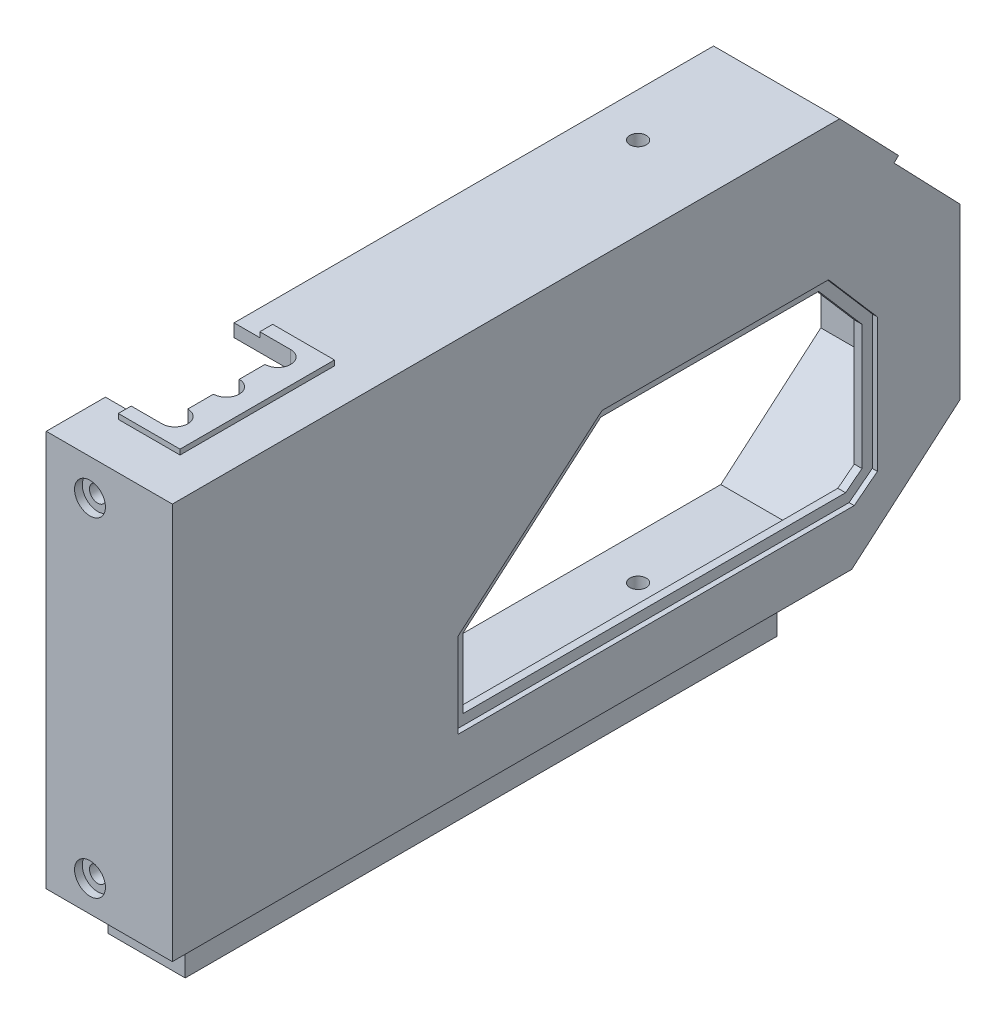
SolidWorks part; units mm, degrees
ref_plane "Front Plane" through (0, 0, 0) normal (0, 0, 1) x (1, 0, 0)
ref_plane "Top Plane" through (0, 0, 0) normal (0, 1, 0) x (1, 0, 0)
ref_plane "Right Plane" through (0, 0, 0) normal (1, 0, 0) x (0, 0, -1)
sketch "Sketch1" plane through (0, 0, 0) normal (1, 0, 0) x (0, 0, -1)
  line L0 (0, 0) -> (0, 77)
  line L1 (0, 77) -> (128, 77)
  line L2 (128, 77) -> (153, 51)
  line L3 (153, 51) -> (153, 18)
  line L4 (153, 18) -> (132, 0)
  line L5 (132, 0) -> (0, 0)
  dimension "D1" = 132
  dimension "D2" = 77
  dimension "D3" = 128
  dimension "D4" = 26
  dimension "D5" = 153
  dimension "D6" = 18
extrude "Base" add sketch "Sketch1" along normal blind 2.5
sketch "Sketch11" plane through (0, 0, 0) normal (-1, 0, 0) x (0, 0, 1)
  line L12 (-131.0752, 2.5) -> (-2.5, 2.5)
  line L13 (-2.5, 2.5) -> (-2.5, 74.5)
  line L14 (-2.5, 74.5) -> (-126.9356, 74.5)
  line L15 (-126.9356, 74.5) -> (-150.5, 49.9931)
  line L16 (-150.5, 49.9931) -> (-150.5, 19.1498)
  line L17 (-150.5, 19.1498) -> (-131.0752, 2.5)
  line L18 (-131.0752, 2.5) -> (-2.5, 2.5)
  line L19 (-2.5, 2.5) -> (-2.5, 74.5)
  line L20 (-2.5, 74.5) -> (-126.9356, 74.5)
  line L21 (-126.9356, 74.5) -> (-150.5, 49.9931)
  line L22 (-150.5, 49.9931) -> (-150.5, 19.1498)
  line L23 (-150.5, 19.1498) -> (-131.0752, 2.5)
  line M7 (-132, 0) -> (0, 0)
  line M8 (0, 0) -> (0, 77)
  line M9 (0, 77) -> (-128, 77)
  line M10 (-128, 77) -> (-153, 51)
  line M11 (-153, 51) -> (-153, 18)
  line M12 (-153, 18) -> (-132, 0)
  dimension "D1" = 2.5
extrude "Boss-Extrude6" add sketch "Sketch11" along normal blind 22 contours L23 L22 L21 L20 L19 L18 M12 M7 M8 M9 M10 M11 region at (0, 10.3005, -141.3853)
ref_plane "Middle" through (-11, 0, 0) normal (1, 0, 0) x (0, 0, -1)
ref_plane "Screw_Mounts" through (-13.5, 0, 0) normal (-1, 0, 0) x (0, 0, 1)
sketch "Sketch14" plane through (0, 0, 0) normal (0, 0, 1) x (1, 0, 0)
  line L1 (-22, 0) -> (-22, 77) construction
  line L2 (-22, 74.5) -> (-10.5, 74.5)
  line L3 (-22, 74.5) -> (-22, 66.5)
  line L4 (-22, 66.5) -> (-10.5, 66.5)
  line L5 (-10.5, 74.5) -> (-10.5, 66.5)
  line L6 (-22, 2.5) -> (-10.5, 2.5)
  line L7 (-22, 2.5) -> (-22, 10.5)
  line L8 (-22, 10.5) -> (-10.5, 10.5)
  line L9 (-10.5, 2.5) -> (-10.5, 10.5)
  line L11 (-13.5, 42.35) -> (-13.5, -42.35) construction
  dimension "D5" = 8
  dimension "D1" = 8
  dimension "D3" = 3
extrude "Boss-Extrude7" add sketch "Sketch14" against normal blind 5
sketch "Sketch15" plane through (0, 0, 0) normal (0, 0, 1) x (1, 0, 0)
  line L0 (-13.5, 42.35) -> (-13.5, -42.35) construction
  circle A0 centre (-13.5, 70) radius 3
  circle A1 centre (-13.5, 6) radius 3
  dimension "D1" = 6
  dimension "D2" = 70
  dimension "D3" = 6
extrude "Cut-Extrude3" cut sketch "Sketch15" against normal blind 1.5
sketch "Sketch16" plane through (0, 0, -1.5) normal (0, 0, 1) x (1, 0, 0)
  circle A0 centre (-13.5, 70) radius 1.6
  circle A1 centre (-13.5, 6) radius 1.6
  dimension "D1" = 3.2
extrude "Cut-Extrude4" cut sketch "Sketch16" against normal up to next
sketch "Sketch12" plane through (0, 0, 0) normal (0, -1, 0) x (1, 0, 0)
  line L2 (-13.5, 42.35) -> (-13.5, -42.35) construction
  circle A1 centre (-13.5, -106.5) radius 1.6
  dimension "D3" = 3.2
  dimension "D1" = 106.5
extrude "Cut-Extrude1" cut sketch "Sketch12" against normal through all
sketch "Sketch17" plane through (0, 77, 0) normal (0, 1, 0) x (1, 0, 0)
  line L5 (-11, -42.9) -> (-11, 42.9) construction
  line L6 (-5, 39) -> (-17, 39)
  line L7 (-5, 39) -> (-5, 9)
  line L8 (-5, 9) -> (-17, 9)
  line L9 (-17, 39) -> (-17, 9)
  line L10 (-5, 39) -> (-17, 9) construction
  line L11 (-5, 9) -> (-17, 39) construction
  line L12 (2.5, 0) -> (-22, 0) construction
  point P0 (-11, 24)
  dimension "D1" = 12
  dimension "D2" = 30
  dimension "D3" = 24
extrude "Boss-Extrude8" add sketch "Sketch17" along normal blind 1
sketch "Sketch13" plane through (0, 78, 0) normal (0, 1, 0) x (1, 0, 0)
  line L0 (-22, 11.5) -> (-11, 11.5)
  line L1 (-22, 0) -> (-22, 128) construction
  line L2 (-11, 16.5) -> (-11, 21.5)
  line L3 (-11, 26.5) -> (-11, 31.5)
  line L4 (-11, 36.5) -> (-22, 36.5)
  line L5 (-22, 36.5) -> (-22, 11.5)
  line L6 (-5, 9) -> (-5, 39) construction
  line L7 (-11, -42.9) -> (-11, 42.9) construction
  arc A0 (-11, 11.5) -> (-11, 16.5) centre (-11, 14) ccw
  arc A1 (-11, 21.5) -> (-11, 26.5) centre (-11, 24) ccw
  arc A2 (-11, 31.5) -> (-11, 36.5) centre (-11, 34) ccw
  point P9 (-5, 24)
  dimension "D1" = 5
  dimension "D4" = 10
  dimension "D5" = 10
extrude "Cut-Extrude2" cut sketch "Sketch13" against normal up to next
sketch "Sketch19" plane through (2.5, 0, 0) normal (1, 0, 0) x (0, 0, -1)
  line L0 (128, 77) -> (129.6647, 77)
  line L1 (129.6647, 77) -> (141.101, 65.1063)
  line L2 (141.101, 65.1063) -> (140.236, 64.2745)
  line L3 (153, 51) -> (128, 77) construction
  line L4 (140.236, 64.2745) -> (128, 77)
  dimension "D1" = 1.2
  dimension "D2" = 16.5
extrude "Boss-Extrude9" add sketch "Sketch19" against normal up to vertex (24.5 mm away) up to point (-22, 77, -128)
sketch "Sketch20" plane through (0, 101.7733, -105.8442) normal (0, 0.6931, -0.7208) x (-1, 0, 0)
  line L1 (11, 42.9) -> (11, -42.9) construction
  line L2 (2.5, -50.8676) -> (19.5, -50.8676)
  line L3 (2.5, -50.8676) -> (2.5, -42.3676)
  line L4 (2.5, -42.3676) -> (19.5, -42.3676)
  line L5 (19.5, -50.8676) -> (19.5, -42.3676)
  line L6 (2.5, -50.8676) -> (19.5, -42.3676) construction
  line L7 (2.5, -42.3676) -> (19.5, -50.8676) construction
  line L8 (-2.5, -50.8676) -> (-2.5, -34.3676) construction
  line L9 (22, -34.3676) -> (-2.5, -34.3676) construction
  line L10 (22, -50.8676) -> (-2.5, -50.8676) construction
  point P2 (11, -46.6176)
  dimension "D1" = 5
  dimension "D2" = 8
extrude "Cut-Extrude5" cut sketch "Sketch20" against normal up to vertex (1.2 mm away) up to point (2.5, 64.2745, -140.236)
sketch "Sketch21" plane through (0, 100.9416, -104.9792) normal (0, 0.6931, -0.7208) x (-1, 0, 0)
  line L0 (11, 42.9) -> (11, -42.9) construction
  line L1 (19.5, -42.3676) -> (2.5, -42.3676) construction
  line L2 (11, -45.8676) -> (22, -45.8676)
  line L3 (22, -45.8676) -> (22, -50.8676)
  line L4 (22, -50.8676) -> (22, -69.2831) construction
  line L5 (11, -50.8676) -> (22, -50.8676)
  line L6 (22, 45.7313) -> (22, 47.5334) construction
  arc A0 (11, -45.8676) -> (11, -50.8676) centre (11, -48.3676) ccw
  dimension "D1" = 5
  dimension "D2" = 6
extrude "Cut-Extrude6" cut sketch "Sketch21" against normal mid plane 10
sketch "Sketch22" plane through (0, 0, 0) normal (0, -1, 0) x (1, 0, 0)
  line L0 (-11, -42.9) -> (-11, 42.9) construction
  line L1 (-18.5, -8.5) -> (-3.5, -8.5)
  line L2 (-18.5, -8.5) -> (-18.5, -123.5)
  line L3 (-18.5, -123.5) -> (-3.5, -123.5)
  line L4 (-3.5, -8.5) -> (-3.5, -123.5)
  line L5 (-18.5, -8.5) -> (-3.5, -123.5) construction
  line L6 (-18.5, -123.5) -> (-3.5, -8.5) construction
  line L7 (2.5, 0) -> (2.5, -132) construction
  point P0 (-11, -66)
  point P5 (0, 0)
  point P6 (0, 0)
  point P11 (2.5, -66)
  dimension "D1" = 115
  dimension "D2" = 15
extrude "Boss-Extrude10" add sketch "Sketch22" along normal blind 10
sketch "Sketch23" plane through (0, -10, 0) normal (0, -1, 0) x (1, 0, 0)
  line L4 (-18.5, -8.5) -> (-18.5, -123.5) construction
  line L5 (-5.5, -10.5) -> (-16.5, -10.5)
  line L6 (-5.5, -10.5) -> (-5.5, -60.5)
  line L7 (-5.5, -60.5) -> (-16.5, -60.5)
  line L8 (-16.5, -10.5) -> (-16.5, -60.5)
  line L9 (-3.5, -123.5) -> (-3.5, -8.5) construction
  line L10 (-3.5, -8.5) -> (-18.5, -8.5) construction
  dimension "D1" = 2
  dimension "D2" = 2
  dimension "D3" = 2
  dimension "D4" = 50
extrude "Cut-Extrude7" cut sketch "Sketch23" against normal up to next
sketch "Sketch24" plane through (0, -10, 0) normal (0, -1, 0) x (1, 0, 0)
  line L0 (-16.5, -10.5) -> (-16.5, -60.5) construction
  line L1 (-5.5, -60.5) -> (-16.5, -60.5)
  line L2 (-5.5, -60.5) -> (-5.5, -121.5)
  line L3 (-5.5, -121.5) -> (-16.5, -121.5)
  line L4 (-16.5, -60.5) -> (-16.5, -121.5)
  line L5 (-18.5, -123.5) -> (-3.5, -123.5) construction
  point P5 (-16.5, -60.5)
  dimension "D1" = 2
extrude "Cut-Extrude8" cut sketch "Sketch24" against normal blind 10
sketch "Sketch25" plane through (2.5, 0, 0) normal (1, 0, 0) x (0, 0, -1)
  line L0 (55.5, 10.5) -> (132.5, 10.5)
  line L1 (132.5, 10.5) -> (137, 14)
  line L2 (137, 14) -> (137, 40)
  line L3 (137, 40) -> (127.5, 51)
  line L4 (127.5, 51) -> (83.5, 51)
  line L5 (83.5, 51) -> (55.5, 27)
  line L6 (55.5, 27) -> (55.5, 10.5)
  dimension "D1" = 77
  dimension "D2" = 4.5
  dimension "D3" = 3.5
  dimension "D4" = 72
  dimension "D5" = 26
  dimension "D6" = 10.5
  dimension "D7" = 55.5
  dimension "D8" = 40.5
  dimension "D9" = 28
  dimension "D10" = 16.5
extrude "Cut-Extrude9" cut sketch "Sketch25" against normal blind 1
sketch "Sketch26" plane through (1.5, 0, 0) normal (1, 0, 0) x (0, 0, -1)
  line L14 (57.5, 26.0801) -> (57.5, 12.5)
  line L15 (57.5, 12.5) -> (131.8138, 12.5)
  line L16 (131.8138, 12.5) -> (135, 14.9782)
  line L17 (135, 14.9782) -> (135, 39.2559)
  line L18 (135, 39.2559) -> (126.5846, 49)
  line L19 (126.5846, 49) -> (84.2398, 49)
  line L20 (84.2398, 49) -> (57.5, 26.0801)
  line L21 (57.5, 26.0801) -> (57.5, 12.5)
  line L22 (57.5, 12.5) -> (131.8138, 12.5)
  line L23 (131.8138, 12.5) -> (135, 14.9782)
  line L24 (135, 14.9782) -> (135, 39.2559)
  line L25 (135, 39.2559) -> (126.5846, 49)
  line L26 (126.5846, 49) -> (84.2398, 49)
  line L27 (84.2398, 49) -> (57.5, 26.0801)
  dimension "D1" = 2
extrude "Cut-Extrude10" cut sketch "Sketch26" against normal up to next
equation "\"D5@Sketch13\"=\"D4@Sketch13\""
equation "\"D1@Sketch14\"=\"D5@Sketch14\""
equation "\"D2@Sketch23\"=\"D1@Sketch23\""
equation "\"D3@Sketch23\"=\"D1@Sketch23\""
